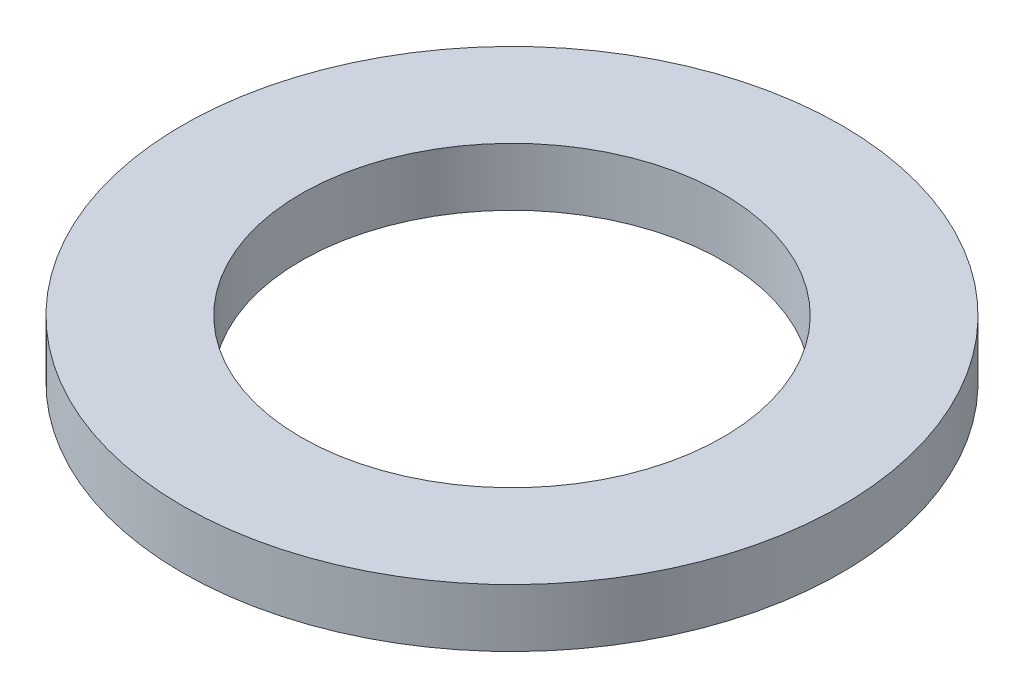
SolidWorks part; units mm, degrees
ref_plane "Front Plane" through (0, 0, 0) normal (0, 0, 1) x (1, 0, 0)
ref_plane "Top Plane" through (0, 0, 0) normal (0, 1, 0) x (1, 0, 0)
ref_plane "Right Plane" through (0, 0, 0) normal (1, 0, 0) x (0, 0, -1)
sketch "Sketch1" plane through (0, 0, 0) normal (0, 1, 0) x (1, 0, 0)
  circle A0 centre (0, 0) radius 62.5
  dimension "FLANGE_OD" = 125
extrude "Boss-Extrude1" add sketch "Sketch1" along normal blind 11
sketch "Sketch2" plane through (0, 0, 0) normal (0, 1, 0) x (1, 0, 0)
  circle A0 centre (0, 0) radius 40
  dimension "BORE_D" = 80
extrude "Cut-Extrude1" cut sketch "Sketch2" along normal through all
sketch "Sketch3" plane through (0, 11, 0) normal (0, 1, 0) x (1, 0, 0)
  circle A0 centre (0, 0) radius 27.3319 construction
  circle A1 centre (-27.3319, 0) radius 3.3029
  dimension "BOLT_D" = 6.6057
  dimension "BOLT_PCD" = 54.6638
extrude "Cut-Extrude2" cut sketch "Sketch3" against normal blind 6.8342 rebuild error yes
pattern_circular "CirPattern1" count 6 over 360 rebuild error yes
